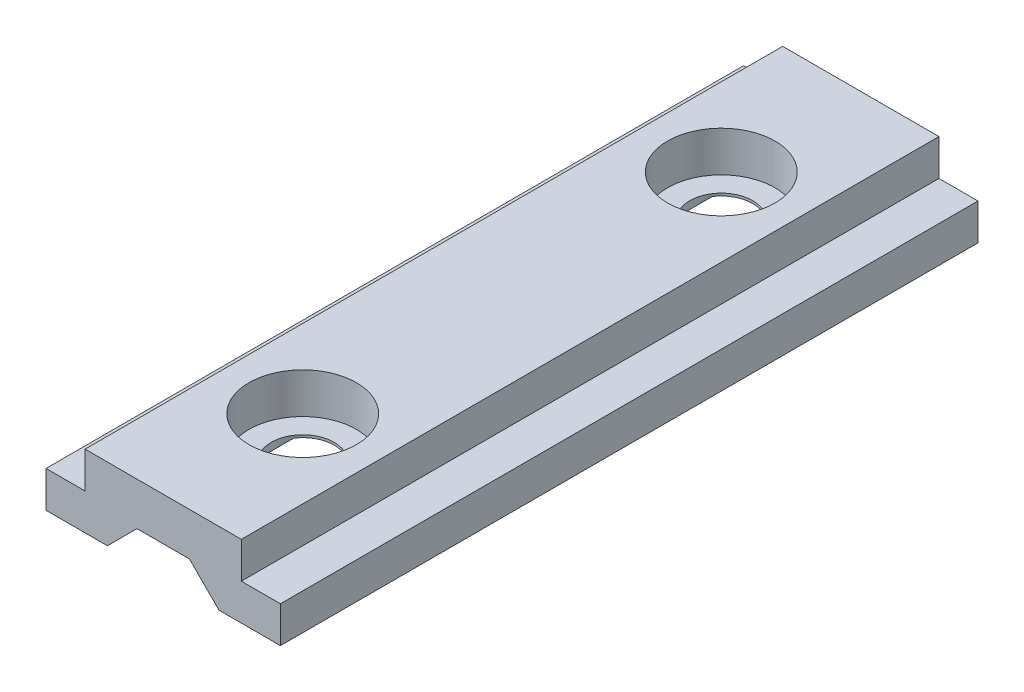
SolidWorks part; units mm, degrees
ref_plane "正面" through (0, 0, 0) normal (0, 0, 1) x (1, 0, 0)
ref_plane "平面" through (0, 0, 0) normal (0, 1, 0) x (1, 0, 0)
ref_plane "右側面" through (0, 0, 0) normal (1, 0, 0) x (0, 0, -1)
sketch "ｽｹｯﾁ1" plane through (0, 0, 0) normal (0, 0, 1) x (1, 0, 0)
  line L0 (0, 0) -> (4.4, 0)
  line L1 (4.4, 0) -> (6.5201, 2.1201)
  line L2 (6.5201, 2.1201) -> (10.2799, 2.1201)
  line L3 (10.2799, 2.1201) -> (12.4, 0)
  line L4 (12.4, 0) -> (16.8, 0)
  line L5 (16.8, 0) -> (16.8, 2.6)
  line L6 (16.8, 2.6) -> (14, 2.6)
  line L7 (14, 2.6) -> (14, 5.2)
  line L8 (14, 5.2) -> (2.8, 5.2)
  line L9 (2.8, 5.2) -> (2.8, 2.6)
  line L10 (2.8, 2.6) -> (0, 2.6)
  line L11 (0, 2.6) -> (0, 0)
extrude "ﾎﾞｽ - 押し出し1" add sketch "ｽｹｯﾁ1" along normal blind 50
sketch "ｽｹｯﾁ2" plane through (0, 5.2, 0) normal (0, 1, 0) x (1, 0, 0)
  line L0 (8.4, 0) -> (8.4, -50)
  line L1 (14, 0) -> (2.8, 0) construction
  line L2 (14, -50) -> (2.8, -50) construction
  line L3 (2.8, -50) -> (2.8, -40)
  line L4 (2.8, -50) -> (2.8, 0) construction
  line L5 (2.8, 0) -> (2.8, -10)
  line L6 (14, -10) -> (14, 0)
  line L7 (14, -50) -> (14, 0) construction
  line L8 (14, -50) -> (14, 0) construction
  line L9 (14, -50) -> (14, -40)
  line L10 (2.8, -10) -> (8.4, -10)
  line L11 (8.4, -10) -> (14, -10)
  line L12 (2.8, -40) -> (8.4, -40)
  line L13 (8.4, -40) -> (14, -40)
hole_wizard "M4 丸平ねじ用座ぐり穴1" positions "3Dｽｹｯﾁ1" profile "ｽｹｯﾁ3" counterbore size "M4" standard "JIS" end condition through all
sketch3d "3Dｽｹｯﾁ1"
  point P0 (8.4, 5.2, 10)
  point P3 (8.4, 5.2, 40)
sketch "ｽｹｯﾁ3" plane through (8.4, 5.2, 10) normal (1, 0, 0) x (0, 0, 1)
  line L0 (0, 0) -> (0, 5.2)
  line L1 (0, 5.2) -> (2.25, 5.2)
  line L3 (2.25, 5.2) -> (2.25, 2.9)
  line L4 (2.25, 2.9) -> (3.85, 2.9)
  line L5 (3.85, 2.9) -> (3.85, 0)
  line L7 (3.85, 0) -> (0, 0)
  line L11 (0, -6.35) -> (0, 107.95) construction
  dimension "通し穴の直径" = 4.5
  dimension "通し穴の深さ" = 5.2
  dimension "座ぐり穴の直径" = 7.7
  dimension "座ぐり穴の深さ" = 2.9
